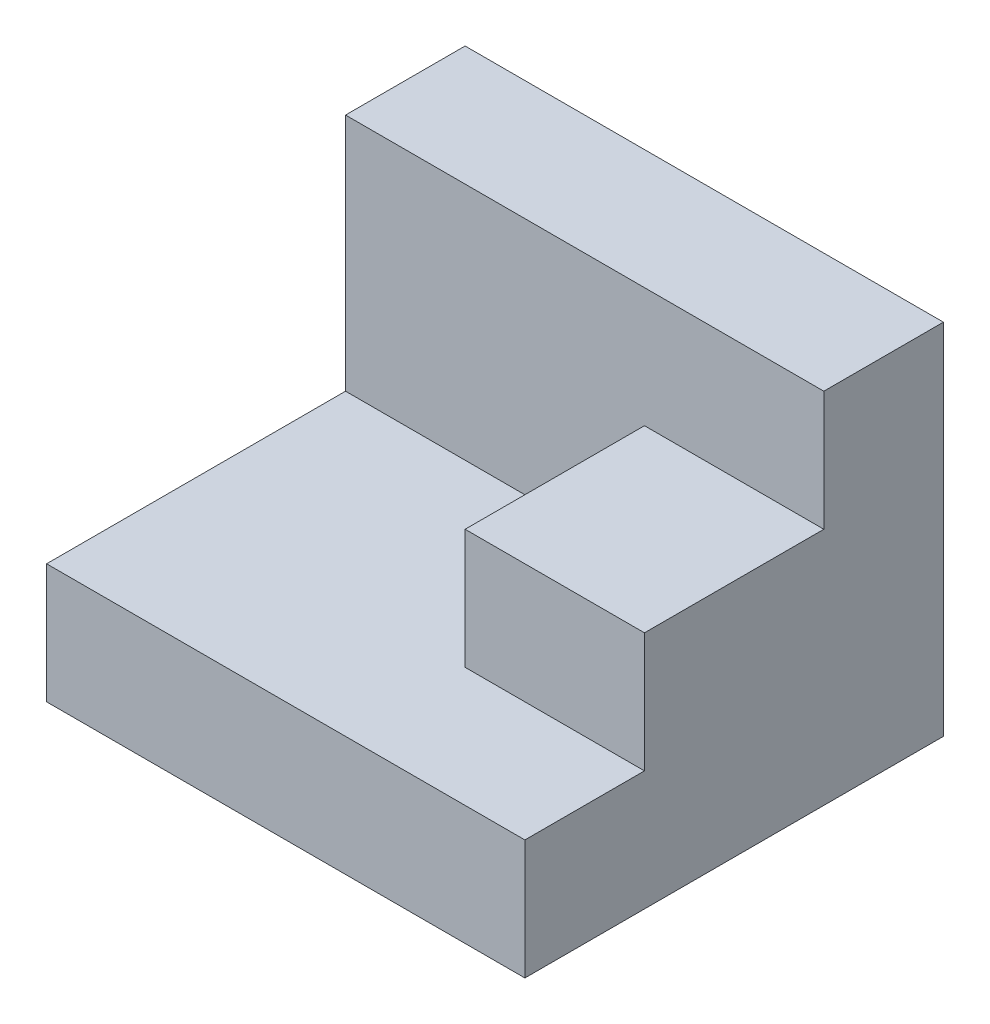
SolidWorks part; units mm, degrees
ref_plane "Front Plane" through (0, 0, 0) normal (0, 0, 1) x (1, 0, 0)
ref_plane "Top Plane" through (0, 0, 0) normal (0, 1, 0) x (1, 0, 0)
ref_plane "Right Plane" through (0, 0, 0) normal (1, 0, 0) x (0, 0, -1)
sketch "Sketch1" plane through (0, 0, 0) normal (0, 0, 1) x (1, 0, 0)
  line L0 (0, 0) -> (40, 0)
  line L1 (40, 0) -> (40, 30)
  line L2 (40, 30) -> (0, 30)
  line L3 (0, 30) -> (0, 0)
  line L4 (40, 20) -> (25, 20)
  line L5 (25, 20) -> (25, 10)
  line L6 (25, 10) -> (40, 10)
  line L7 (0, 10) -> (40, 10)
  dimension "D1" = 10
  dimension "D2" = 10
  dimension "D3" = 40
  dimension "D4" = 15
  dimension "D5" = 10
  dimension "D6" = 30
extrude "Boss-Extrude1" add sketch "Sketch1" along normal blind 10 contours L7 L3 L0 L1 L6 | L5 L6 L1 L4 | L3 L7 L5 L4 L1 L2 region at (20, 5, 0) region at (17.1154, 21.1538, 0) region at (32.5, 15, 0)
extrude "Boss-Extrude2" add sketch "Sketch1<3>" along normal blind 25 contours L5 L6 L1 L4 region at (32.5, 15, 0)
sketch "Sketch1<3>" plane through (0, 0, 0) normal (0, 0, 1) x (1, 0, 0) same geometry as "Sketch1"
extrude "Boss-Extrude4" add sketch "Sketch1<5>" along normal blind 35 contours L7 L3 L0 L1 L6 region at (20, 5, 0)
sketch "Sketch1<5>" plane through (0, 0, 0) normal (0, 0, 1) x (1, 0, 0) same geometry as "Sketch1"
